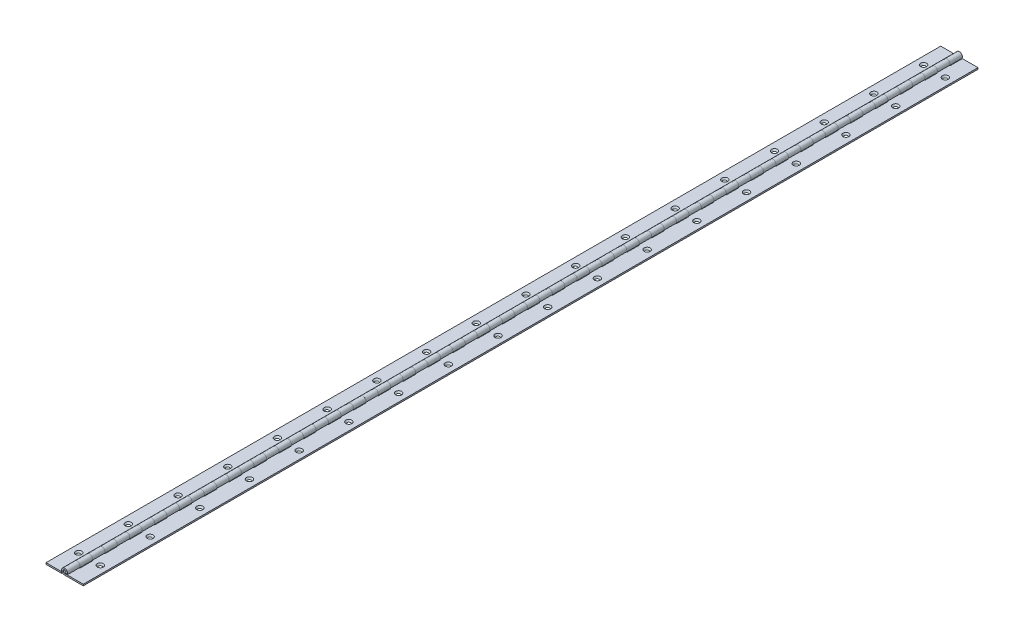
SolidWorks part; units mm, degrees
note: '?' marks a value the reader was unsure of.
ref_plane "Front Plane" through (0, 0, 0) normal (0, 0, 1) x (1, 0, 0)
ref_plane "Top Plane" through (0, 0, 0) normal (0, 1, 0) x (1, 0, 0)
ref_plane "Right Plane" through (0, 0, 0) normal (1, 0, 0) x (0, 0, -1)
sketch "Sketch1" plane through (0, 0, 0) normal (0, 0, 1) x (1, 0, 0)
  line L0 (2.6761, -1.5875) -> (19.05, -1.5875)
  line L1 (19.05, -1.5875) -> (19.05, -3.1115)
  line L2 (19.05, -3.1115) -> (0, -3.1115)
  line L3 (0, 0) -> (0, 1.5875) construction
  line L4 (-1.5875, 0) -> (-3.1115, 0) construction
  line L5 (1.4388, -0.6709) -> (2.82, -1.315) construction
  line L6 (-1.4388, -0.6709) -> (-2.82, -1.315) construction
  circle A0 centre (0, 0) radius 1.5875
  circle A1 centre (0, 0) radius 3.1115
  dimension "knuckle dia" = 6.223
  dimension "leaf thickness" = 1.524
  dimension "open width" = 38.1
  dimension "D5" = 25
  dimension "D6" = 25
sketch "Sketch2" plane through (0, 0, 0) normal (0, 0, 1) x (1, 0, 0)
  line L0 (19.05, -1.5875) -> (19.05, -3.1115) construction
  line L1 (2.6761, -1.5875) -> (19.05, -1.5875) construction
  line L2 (1.4388, -0.6709) -> (2.82, -1.315) construction
  line L3 (19.05, -3.1115) -> (0, -3.1115) construction
  line L4 (19.05, -1.5875) -> (19.05, -3.1115)
  line L5 (0, -1.5875) -> (19.05, -1.5875)
  line L6 (1.4388, -0.6709) -> (2.82, -1.315)
  line L7 (19.05, -3.1115) -> (0, -3.1115)
  circle A0 centre (0, 0) radius 1.5875 construction
  circle A1 centre (0, 0) radius 3.1115 construction
  arc A2 (1.4388, -0.6709) -> (0, -1.5875) centre (0, 0) ccw
  arc A3 (2.82, -1.315) -> (0, -3.1115) centre (0, 0) ccw
extrude "Extrude1" add sketch "Sketch2" along normal mid plane 914.4
sketch "Sketch3" plane through (0, -1.5875, 0) normal (0, 1, 0) x (1, 0, 0)
  line L1 (-3.1115, 457.2) -> (3.1115, 457.2)
  line L2 (-3.1115, 457.2) -> (-3.1115, 444.5)
  line L3 (-3.1115, 444.5) -> (3.1115, 444.5)
  line L4 (3.1115, 457.2) -> (3.1115, 444.5)
  line L5 (3.1115, 457.2) -> (-3.1115, 457.2) construction
  line L7 (3.1115, -457.2) -> (3.1115, 457.2) construction
  line L8 (-3.1115, 457.2) -> (-3.1115, -457.2) construction
  dimension "knuckle length" = 12.7
extrude "Cut-Extrude1" cut sketch "Sketch3" against normal mid plane 50.8
pattern_linear "LPattern1" count 36 spacing 25.4 along (0, 0, 1) of "Cut-Extrude1"
sketch "Sketch5" plane through (0, 0, -457.2) normal (0, 0, -1) x (-1, 0, 0)
  line L0 (-2.6761, -1.5875) -> (-19.05, -1.5875) construction
  line L1 (-19.05, -3.1115) -> (0, -3.1115) construction
  line L2 (0, -1.5875) -> (19.05, -1.5875)
  line L3 (19.05, -3.1115) -> (0, -3.1115)
  line L4 (1.4388, -0.6709) -> (2.82, -1.315) construction
  line L5 (1.4388, -0.6709) -> (2.82, -1.315)
  line L6 (19.05, -1.5875) -> (19.05, -3.1115)
  line L8 (0, 0) -> (0, -3.1115) construction
  circle A0 centre (0, 0) radius 3.1115 construction
  arc A1 (2.82, -1.315) -> (0, -3.1115) centre (0, 0) ccw
  circle A2 centre (0, 0) radius 1.5875 construction
  arc A3 (1.4388, -0.6709) -> (0, -1.5875) centre (0, 0) ccw
  dimension "D1" = 38.1
extrude "Extrude2" add sketch "Sketch5" against normal blind 12.7 separate body
pattern_linear "LPattern3" count 36 spacing 25.4 along (0, 0, 1) of bodies 104
sketch "Sketch6" plane through (0, 0, -457.2) normal (0, 0, -1) x (-1, 0, 0)
  line L0 (0, -3.1115) -> (19.05, -3.1115) construction
  line L1 (19.05, -1.5875) -> (3.1369, -1.5875)
  line L2 (19.05, -1.5875) -> (19.05, -3.1115)
  line L3 (19.05, -3.1115) -> (3.1369, -3.1115)
  line L4 (3.1369, -1.5875) -> (3.1369, -3.1115)
  line L6 (19.05, -1.5875) -> (0, -1.5875) construction
  line L7 (3.1115, 1.5054) -> (3.1115, -2.5761) construction
  arc A0 (2.82, -1.315) -> (0, -3.1115) centre (0, 0) ccw construction
  dimension "D1" = 0.0254
extrude "Extrude5" add sketch "Sketch6" against normal blind 914.4
sketch "Sketch10" plane through (0, -3.1115, 0) normal (0, 1, 0) x (1, 0, 0)
  line L0 (19.05, -457.2) -> (19.05, 457.2) construction
  line L2 (19.05, 457.2) -> (3.1115, 457.2) construction
  circle A0 centre (11.1125, 431.8) radius 1.7526
  point P2 (11.0807, 457.2)
  dimension "hole dia" = 3.5052
  dimension "A" = 25.4
  dimension "D" = 7.9375
extrude "Cut-Extrude2" cut sketch "Sketch10" along normal through all draft 41 draft outward yes
pattern_linear "LPattern4" count 18 spacing 50.8 along (0, 0, 1) of "Cut-Extrude2"
mirror "Mirror3" about plane through (0, 0, 0) normal (1, 0, 0) of "LPattern4", "Cut-Extrude2"
sketch "Sketch7" plane through (0, 0, 0) normal (0, 0, 1) x (1, 0, 0)
  circle A0 centre (0, 0) radius 1.5875 construction
  circle A1 centre (0, 0) radius 1.5875
extrude "Extrude4" add sketch "Sketch7" along normal mid plane 914.4 separate body
chamfer "Chamfer1" distance 0.3175 angle 45 2 edges at (1.5875, 0, 457.2) (1.5875, 0, -457.2)
sketch "Sketch8" plane through (0, 0, 0) normal (0, 1, 0) x (1, 0, 0)
  line L0 (19.05, 0) -> (-19.05, 0) construction
  line L1 (19.05, 0) -> (0, 0) construction
  line L2 (-19.05, -457.2) -> (-19.05, 457.2) construction
  line L3 (19.05, -457.2) -> (19.05, 457.2) construction
ref_axis "Axis1" through (-19.05, 0, 0) along (1, 0, 0)?
ref_plane "  " through (0, 0, 0) normal (0, 0.866, 0.5) x (1, 0, 0)
sketch "Sketch9" plane through (0, 0, 0) normal (0, 1, 0) x (1, 0, 0)
  line L0 (3.1115, 444.5) -> (3.1115, 457.2) construction
  point P0 (-19.05, 457.2)
  point P1 (19.05, 457.2)
  point P3 (-19.05, -457.2)
  point P5 (19.05, -457.2)
  point P7 (3.1115, 444.5)
sketch "Sketch11" plane through (0, 0, 0) normal (0, 0, 1) x (1, 0, 0)
  line L0 (-3.1115, 0) -> (-3.1115, -3.1115) construction
  line L1 (-3.1115, -3.1115) -> (3.1115, -3.1115) construction
  line L2 (3.1115, -3.1115) -> (3.1115, 0) construction
  line L3 (0, -3.1115) -> (19.05, -3.1115) construction
  circle A0 centre (0, 0) radius 3.1115
  circle A2 centre (0, 0) radius 3.1115 construction
equation "\"D1@LPattern1\" = \"overall length@Extrude1\"/(\"knuckle length@Sketch3\"*2)"
equation "\"D1@Sketch5\" = \"open width@Sketch1\""
equation "\"D1@LPattern3\" = \"D1@LPattern1\""
equation "\"D1@Extrude4\" = \"overall length@Extrude1\""
equation "\"D3@LPattern1\" = \"knuckle length@Sketch3\"*2"
equation "\"D3@LPattern3\" = \"D3@LPattern1\""
equation "\"D1@Chamfer1\" = \"pin diameter@Sketch1\"*.1"
equation "\"D1@Extrude2\" = \"knuckle length@Sketch3\""
equation "\"D1@Extrude5\" = \"overall length@Extrude1\""
equation "\"D1@LPattern4\" = \"overall length@Extrude1\"/2"
